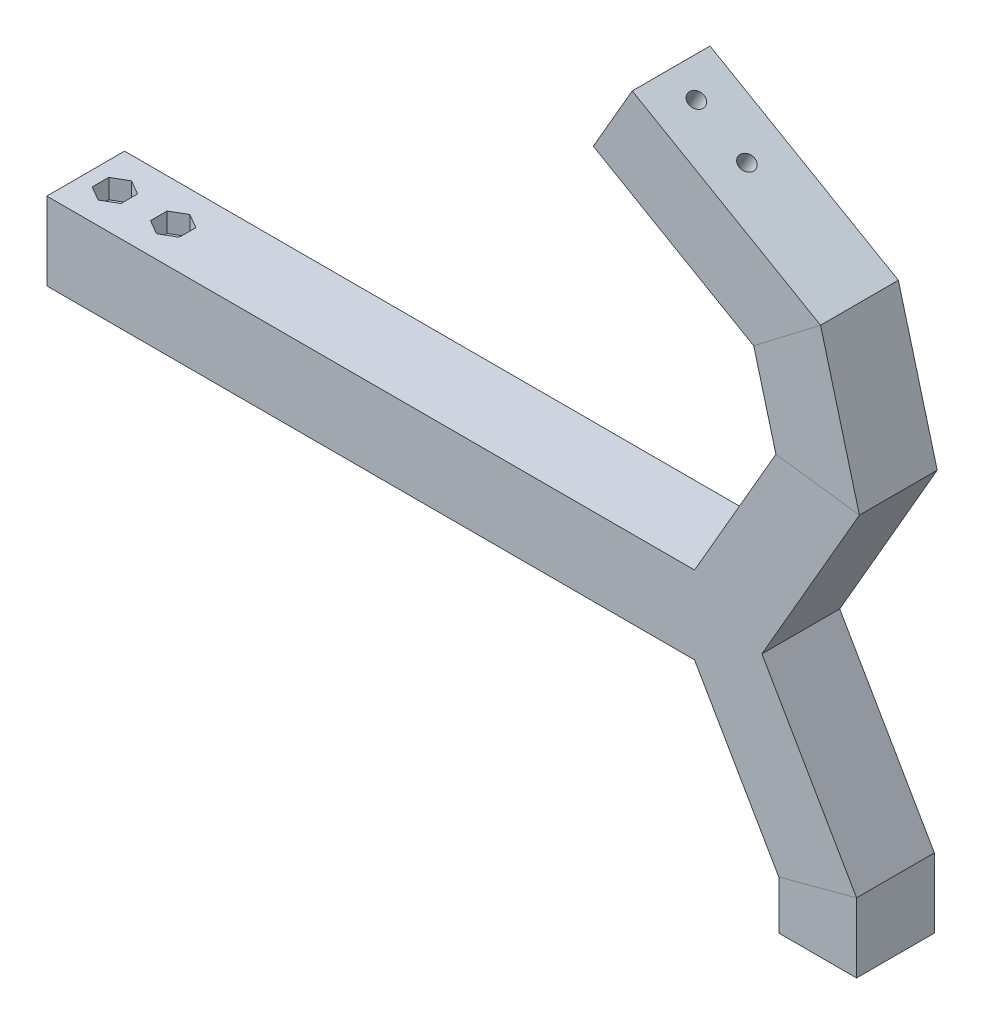
SolidWorks part; units mm, degrees
ref_plane "Front Plane" through (0, 0, 0) normal (0, 0, 1) x (1, 0, 0)
ref_plane "Top Plane" through (0, 0, 0) normal (0, 1, 0) x (1, 0, 0)
ref_plane "Right Plane" through (0, 0, 0) normal (1, 0, 0) x (0, 0, -1)
sketch "Sketch1" plane through (0, 0, 0) normal (0, 0, 1) x (1, 0, 0)
  line L0 (0, 0) -> (44.8288, -25.8819)
  line L1 (44.8288, -25.8819) -> (52.6768, -55.1712)
  line L2 (52.6768, -55.1712) -> (26.7949, -100)
  line L3 (0, 0) -> (26.7949, -100) construction
  line L4 (26.7949, -100) -> (-145.5051, -100)
  line L5 (26.7949, -100) -> (52.6768, -144.8288)
  line L6 (52.6768, -144.8288) -> (52.6768, -160)
  circle A0 centre (13.3975, -50) radius 36.6025 construction
  point P9 (52.6768, -192.5215)
  dimension "D1" = 135
  dimension "D2" = 30
  dimension "D3" = 100
  dimension "D4" = 172.3
  dimension "D5" = 120
  dimension "D6" = 60
ref_plane "Plane1" through (0, 0, 0) normal (-0.866, 0.5, 0) x (0, 0, 1)
sketch "Sketch2" plane through (0, 0, 0) normal (-0.866, 0.5, 0) x (0, 0, 1)
  line L1 (-10, -10) -> (10, -10)
  line L2 (-10, -10) -> (-10, 10)
  line L3 (-10, 10) -> (10, 10)
  line L4 (10, -10) -> (10, 10)
  line L5 (-10, -10) -> (10, 10) construction
  line L6 (-10, 10) -> (10, -10) construction
  point P0 (0, 0)
  dimension "D1" = 20
  dimension "D2" = 20
sweep "Sweep1" add profiles "Sketch2" path "Sketch1"
ref_plane "Plane2" through (-145.5051, -100, 0) normal (-1, 0, 0) x (0, 0, 1)
sketch "Sketch4" plane through (-145.5051, -100, 0) normal (-1, 0, 0) x (0, 0, 1)
  line L1 (-10, -10) -> (10, -10)
  line L2 (-10, -10) -> (-10, 10)
  line L3 (-10, 10) -> (10, 10)
  line L4 (10, -10) -> (10, 10)
  line L5 (-10, -10) -> (10, 10) construction
  line L6 (-10, 10) -> (10, -10) construction
  point P0 (0, 0)
  dimension "D1" = 20
  dimension "D2" = 20
sweep "Sweep3" add profiles "Sketch4" path "Sketch1<5>"
sketch "Sketch1<5>" plane through (0, 0, 0) normal (0, 0, 1) x (1, 0, 0) same geometry as "Sketch1"
sketch "Sketch5" plane through (5, 8.6603, 0) normal (0.5, 0.866, 0) x (0.866, -0.5, 0)
  line L0 (0, 0) -> (55.9059, 0) construction
  line L1 (55.9059, 10) -> (55.9059, -10) construction
  line L2 (0, -10) -> (0, 10) construction
  line L3 (7.5, 4.2724) -> (3.8, 2.1362)
  line L4 (3.8, 2.1362) -> (3.8, -2.1362)
  line L5 (3.8, -2.1362) -> (7.5, -4.2724)
  line L6 (7.5, -4.2724) -> (11.2, -2.1362)
  line L7 (11.2, -2.1362) -> (11.2, 2.1362)
  line L8 (11.2, 2.1362) -> (7.5, 4.2724)
  line L9 (22.5, 4.2724) -> (18.8, 2.1362)
  line L10 (18.8, 2.1362) -> (18.8, -2.1362)
  line L11 (18.8, -2.1362) -> (22.5, -4.2724)
  line L12 (22.5, -4.2724) -> (26.2, -2.1362)
  line L13 (26.2, -2.1362) -> (26.2, 2.1362)
  line L14 (26.2, 2.1362) -> (22.5, 4.2724)
  circle A0 centre (7.5, 0) radius 3.7 construction
  circle A1 centre (22.5, 0) radius 3.7 construction
  circle A2 centre (7.5, 0) radius 2
  circle A3 centre (22.5, 0) radius 2
  dimension "D4" = 4
  dimension "D1" = 7.4
  dimension "D2" = 7.5
  dimension "D3" = 15
extrude "Cut-Extrude1" cut sketch "Sketch5" against normal up to next contours A2 | A3 region at (11.4952, 4.9103, 0) region at (24.4856, -2.5897, 0)
extrude "Cut-Extrude2" cut sketch "Sketch5<3>" along normal blind 5 from surface contours L7 L8 L3 L4 L5 L6 A2 | L13 L14 L9 L10 L11 L12 A3 region at (13.0484, 4.0135, -3.1064) region at (26.0388, -3.4865, -3.1064) starting at face at (12.7535, -18.9103, 0)
sketch "Sketch5<3>" plane through (5, 8.6603, 0) normal (0.5, 0.866, 0) x (0.866, -0.5, 0) same geometry as "Sketch5"
sketch "Sketch6" plane through (0, -90, -90) normal (0, 1, 0) x (1, 0, 0)
  line L0 (-145.5051, -90) -> (-5, -90) construction
  line L3 (-138.0051, -85.7276) -> (-141.7051, -87.8638)
  line L4 (-141.7051, -87.8638) -> (-141.7051, -92.1362)
  line L5 (-141.7051, -92.1362) -> (-138.0051, -94.2724)
  line L6 (-138.0051, -94.2724) -> (-134.3051, -92.1362)
  line L7 (-134.3051, -92.1362) -> (-134.3051, -87.8638)
  line L8 (-134.3051, -87.8638) -> (-138.0051, -85.7276)
  line L9 (-123.0051, -85.7276) -> (-126.7051, -87.8638)
  line L10 (-126.7051, -87.8638) -> (-126.7051, -92.1362)
  line L11 (-126.7051, -92.1362) -> (-123.0051, -94.2724)
  line L12 (-123.0051, -94.2724) -> (-119.3051, -92.1362)
  line L13 (-119.3051, -92.1362) -> (-119.3051, -87.8638)
  line L14 (-119.3051, -87.8638) -> (-123.0051, -85.7276)
  line L15 (-145.5051, -100) -> (-145.5051, -80) construction
  line L16 (-5, -80) -> (-5, -100) construction
  circle A0 centre (-138.0051, -90) radius 3.7 construction
  circle A1 centre (-123.0051, -90) radius 3.7 construction
  circle A2 centre (-138.0051, -90) radius 2
  circle A3 centre (-123.0051, -90) radius 2
  point P3 (65.109, -25.249)
  point P4 (-164.7083, -48.9833)
  point P14 (-214.7819, -88.9264)
  point P22 (-145.5051, -90)
  point P27 (-5, -90)
  dimension "D4" = 4
  dimension "D1" = 7.4
  dimension "D2" = 7.5
  dimension "D3" = 15
extrude "Cut-Extrude3" cut sketch "Sketch6" against normal up to next contours A2 | A3 region at (-138.0051, -90, 0) region at (-123.0051, -90, 0)
extrude "Cut-Extrude4" cut sketch "Sketch6<5>" against normal blind 5 contours L7 L8 L3 L4 L5 L6 A2 | L13 L14 L9 L10 L11 L12 A3 region at (-136.2116, -90, -3.1064) region at (-121.2116, -90, -3.1064)
sketch "Sketch6<5>" plane through (0, -90, -90) normal (0, 1, 0) x (1, 0, 0) same geometry as "Sketch6"
